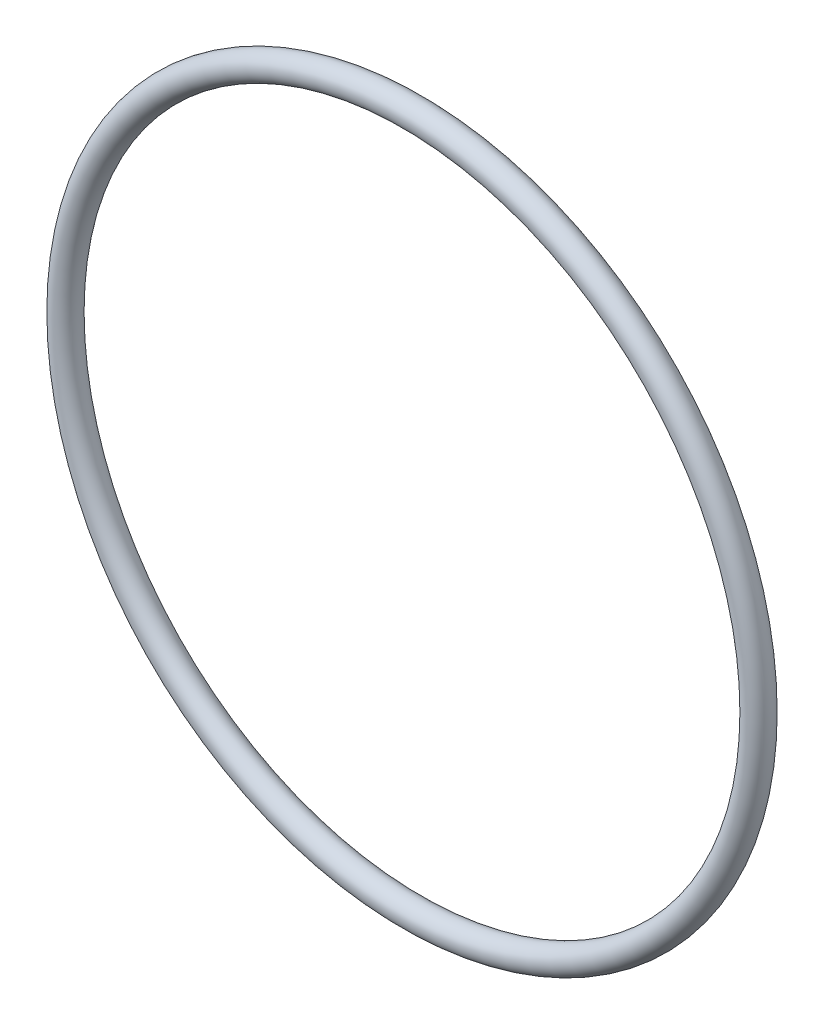
SolidWorks part; units mm, degrees
ref_plane "Front" through (0, 0, 0) normal (0, 0, 1) x (1, 0, 0)
ref_plane "Top" through (0, 0, 0) normal (0, 1, 0) x (1, 0, 0)
ref_plane "Right" through (0, 0, 0) normal (1, 0, 0) x (0, 0, -1)
sketch "Sketch1" plane through (0, 0, 0) normal (0, 0, 1) x (1, 0, 0)
  circle A0 centre (0, 0) radius 33.5
  dimension "d1" = 67
sketch "Sketch2" plane through (0, 0, 0) normal (0, 1, 0) x (1, 0, 0)
  circle A0 centre (-34.825, 0) radius 1.325
  point P2 (-33.5, 0)
  dimension "d2" = 2.65
sweep "Sweep1" add profiles "Sketch2" path "Sketch1"
ref_axis "Axis1" through (0, 0, -4.6197) along (0, 0, 1)
ref_axis "Assi1" through (0, 0, -80.9) along (0, 0, 1)
